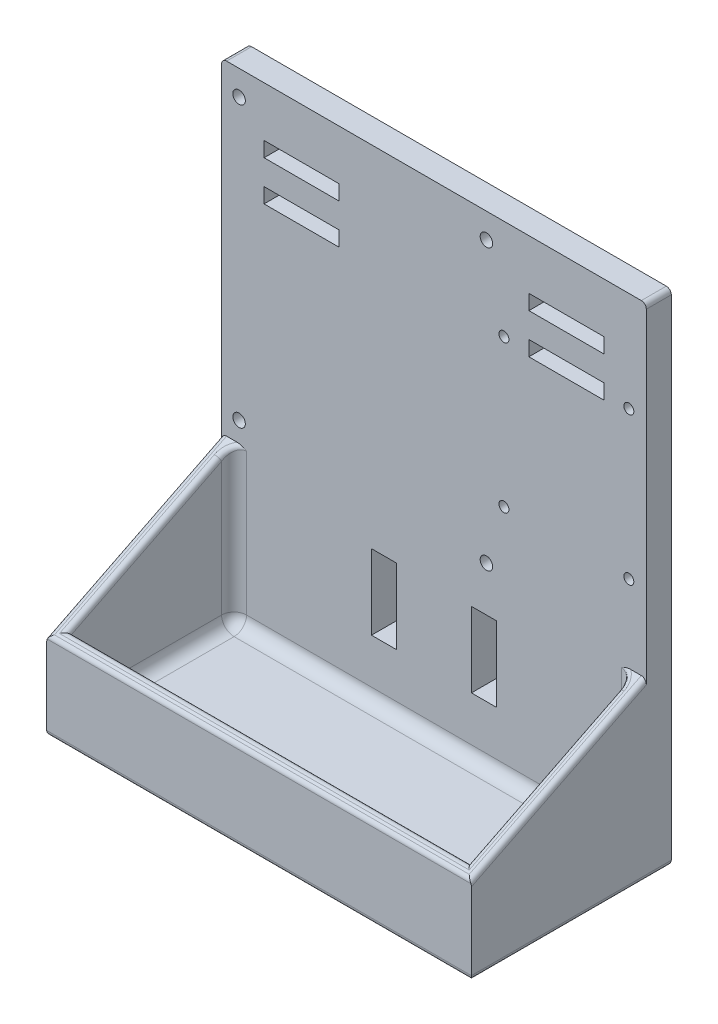
SolidWorks part; units mm, degrees
ref_plane "Front Plane" through (0, 0, 0) normal (0, 0, 1) x (1, 0, 0)
ref_plane "Top Plane" through (0, 0, 0) normal (0, 1, 0) x (1, 0, 0)
ref_plane "Right Plane" through (0, 0, 0) normal (1, 0, 0) x (0, 0, -1)
ref_plane "Plane1" through (0, 0, 0) normal (0, 0, 1) x (1, 0, 0)
sketch "Sketch1" plane through (0, 0, 0) normal (0, 0, 1) x (1, 0, 0)
  line L1 (-85, 100) -> (85, 100)
  line L2 (-85, 100) -> (-85, -100)
  line L3 (-85, -100) -> (85, -100)
  line L4 (85, 100) -> (85, -100)
  line L5 (-85, 100) -> (85, -100) construction
  line L6 (-85, -100) -> (85, 100) construction
  point P0 (0, 0)
  point P1 (0, 0)
extrude "Boss-Extrude4" add sketch "Sketch1" along normal blind 10
sketch "Sketch4" plane through (0, 0, 10) normal (0, 0, 1) x (1, 0, 0)
  line L0 (85, 100) -> (-85, 100) construction
  line L1 (-85, 100) -> (-85, -100) construction
  line L2 (85, -100) -> (85, 100) construction
  line L3 (-85, -35) -> (85, -35)
  line L4 (-85, -100) -> (85, -100) construction
  circle A0 centre (-78, 90) radius 2.5
  circle A4 centre (78, 60) radius 2
  circle A5 centre (21, 90) radius 2.5
  circle A6 centre (21, -22) radius 2.5
  circle A7 centre (-78, -22) radius 2.5
  circle A8 centre (28, 60) radius 2
  circle A9 centre (28, 1) radius 2
  circle A10 centre (78, 1) radius 2
  dimension "D1" = 10
  dimension "D5" = 40
  dimension "D2" = 7
  dimension "D6" = 7
  dimension "D9" = 65
  dimension "D3" = 2
  dimension "D4" = 2
  dimension "D7" = 2
  dimension "D8" = 2
extrude "Cut-Extrude1" cut sketch "Sketch4" against normal through all contours A0 | A7 | A5 | A6 | A9 | A10 | A4 | A8 region at (-78, 90, 10) region at (78, 60, 10) region at (21, 90, 10) region at (21, -22, 10) region at (-78, -22, 10) region at (28, 60, 10) region at (28, 1, 10) region at (78, 1, 10)
sketch "Sketch5" plane through (0, 0, 10) normal (0, 0, 1) x (1, 0, 0)
  line L0 (-85, -30) -> (85, -30)
  line L1 (-85, 100) -> (-85, -100) construction
  line L2 (85, -100) -> (85, 100) construction
  line L3 (-85, -100) -> (85, -100) construction
  line L4 (0, 0) -> (0, -100)
  line L5 (-25, -40) -> (-15, -40)
  line L6 (-25, -40) -> (-25, -70)
  line L7 (-25, -70) -> (-15, -70)
  line L8 (-15, -40) -> (-15, -70)
  line L13 (25, -70) -> (15, -70)
  line L14 (15, -40) -> (15, -70)
  line L15 (25, -40) -> (15, -40)
  line L16 (25, -40) -> (25, -70)
  circle A0 centre (-78, -22) radius 2.5 construction
  dimension "D2" = 8
  dimension "D1" = 70
  dimension "D3" = 10
  dimension "D4" = 30
  dimension "D5" = 10
  dimension "D6" = 60
extrude "Cut-Extrude2" cut sketch "Sketch5" against normal through all contours L8 L5 L6 L7 | L16 L15 L14 L13 region at (-20, -55, 10) region at (20, -55, 10)
sketch "Sketch6" plane through (0, 0, 10) normal (0, 0, 1) x (1, 0, 0)
  line L0 (0, 0) -> (0, 100)
  line L1 (85, 100) -> (-85, 100) construction
  line L2 (-85, 100) -> (-85, -100) construction
  line L3 (-68, 80) -> (-38, 80)
  line L4 (-68, 80) -> (-68, 74)
  line L5 (-68, 74) -> (-38, 74)
  line L6 (-38, 80) -> (-38, 74)
  line L7 (68, 58) -> (38, 58)
  line L8 (-68, 64) -> (-38, 64)
  line L9 (-68, 64) -> (-68, 58)
  line L10 (-68, 58) -> (-38, 58)
  line L11 (-38, 64) -> (-38, 58)
  line L12 (38, 64) -> (38, 58)
  line L13 (68, 64) -> (38, 64)
  line L14 (68, 64) -> (68, 58)
  line L15 (68, 74) -> (38, 74)
  line L16 (38, 80) -> (38, 74)
  line L17 (68, 80) -> (38, 80)
  line L18 (68, 80) -> (68, 74)
  dimension "D1" = 20
  dimension "D2" = 30
  dimension "D3" = 17
  dimension "D4" = 6
  dimension "D5" = 10
  dimension "D6" = 6
extrude "Cut-Extrude3" cut sketch "Sketch6" against normal blind 10 contours L6 L3 L4 L5 | L11 L8 L9 L10 | L18 L17 L16 L15 | L14 L13 L12 L7 region at (-53, 77, 10) region at (53, 61, 10) region at (-53, 61, 10) region at (53, 77, 10)
sketch "Sketch7" plane through (0, 0, 10) normal (0, 0, 1) x (1, 0, 0)
  line L0 (85, -100) -> (85, 100) construction
  line L1 (-85, -100) -> (85, -100)
  line L2 (-85, -100) -> (-85, -93)
  line L3 (-85, -93) -> (85, -93)
  line L4 (85, -100) -> (85, -93)
  line L6 (-85, -100) -> (-80, -100)
  line L7 (-85, -100) -> (-85, -30)
  line L8 (-85, -30) -> (-80, -30)
  line L9 (-80, -100) -> (-80, -30)
  line L10 (85, -100) -> (80, -100)
  line L11 (85, -100) -> (85, -30)
  line L12 (85, -30) -> (80, -30)
  line L13 (80, -100) -> (80, -30)
  circle A0 centre (-78, -22) radius 2.5 construction
  line M15 (85, -100) -> (85, 100)
  line M17 (-85, 100) -> (-85, -100)
  line M18 (-85, -100) -> (85, -100)
  dimension "D2" = 8
  dimension "D1" = 70
  dimension "D3" = 5
  dimension "D4" = 5
  dimension "D5" = 70
extrude "Boss-Extrude5" add sketch "Sketch7" along normal blind 70 contours L13 L3 M18 M15 | L13 L3 L12 M15 | L1 L13 L3 L9 | L9 L3 M18 M17 | L3 L9 L8 M17 region at (-82.5, -96.5, 10) region at (0, -96.5, 10) region at (-82.5, -61.5, 10) region at (82.5, -96.5, 10) region at (82.5, -61.5, 10)
sketch "Sketch8" plane through (-85, 0, 0) normal (-1, 0, 0) x (0, 0, 1)
  line L0 (10, -30) -> (10, -100)
  line L1 (80, -100) -> (0, -100) construction
  line L2 (10, -65) -> (80, -65)
  line L3 (80, -30) -> (80, -100) construction
  line L4 (10, -30) -> (80, -65)
  line L5 (80, -30) -> (10, -30)
  line L6 (80, -30) -> (80, -65)
  line M4 (80, -100) -> (80, -30)
  line M5 (80, -30) -> (10, -30)
  dimension "D1" = 35
extrude "Cut-Extrude4" cut sketch "Sketch8" against normal through all contours L4 M5 M4 region at (-85, -41.6667, 56.6667)
sketch "Sketch9" plane through (-85, 0, 0) normal (-1, 0, 0) x (0, 0, 1)
  line L0 (75, -100) -> (75, -62.5)
  line L1 (80, -100) -> (0, -100) construction
  line L2 (10, -30) -> (80, -65) construction
  line L3 (80, -65) -> (80, -100) construction
  line L4 (75, -62.5) -> (80, -65)
  line L5 (80, -65) -> (80, -100)
  line L6 (80, -100) -> (75, -100)
  dimension "D1" = 5
extrude "Boss-Extrude6" add sketch "Sketch9" against normal up to surface (165 mm away) up to face at (80, -70.25, 45)
fillet "Fillet2" radius 5 1 edges at (0, -93, 10) type face fillet first side face at (0, -13.25, 10) second side face at (0, -93, 42.5)
fillet "Fillet3" radius 5 3 edges at (80, -93, 45) (-80, -93, 45) (0, -93, 75) type face fillet first side face at (-80, -73.5071, 36.7929) first side face at (80, -73.5071, 36.7929) first side face at (0, -77.75, 75) second side face at (0, -93, 45)
fillet "Fillet4" radius 2 4 edges at (0, -100, 0) (85, -100, 40) (-85, -100, 40) (0, -100, 80) type face fillet first side face at (53, 77, 0) first side face at (85, -15.8333, 30) first side face at (0, -82.5, 80) first side face at (-85, -15.8333, 30) second side face at (0, -100, 40)
fillet "Fillet5" radius 2 3 edges at (85, -47.5, 45) (-85, -47.5, 45) (0, -65, 80) type face fillet first side face at (0, -43.8964, 37.7929) second side face at (85, -15.1667, 30) second side face at (0, -81.5, 80) second side face at (-85, -15.1667, 30)
fillet "Fillet6" radius 2 3 edges at (80, -47.5, 45) (-80, -47.5, 45) (0, -62.5, 75) type face fillet first side face at (0, -43.7859, 37.5718) second side face at (80, -67.75, 45) second side face at (0, -75.25, 75) second side face at (-80, -67.75, 45)
fillet "Fillet7" radius 2 1 edges at (-85, 100, 5) type face fillet first side face at (-85, -15.912, 30) second side face at (0, 100, 5)
fillet "Fillet8" radius 2 1 edges at (85, 100, 5) type face fillet first side face at (85, -15.912, 30) second side face at (1, 100, 5)
